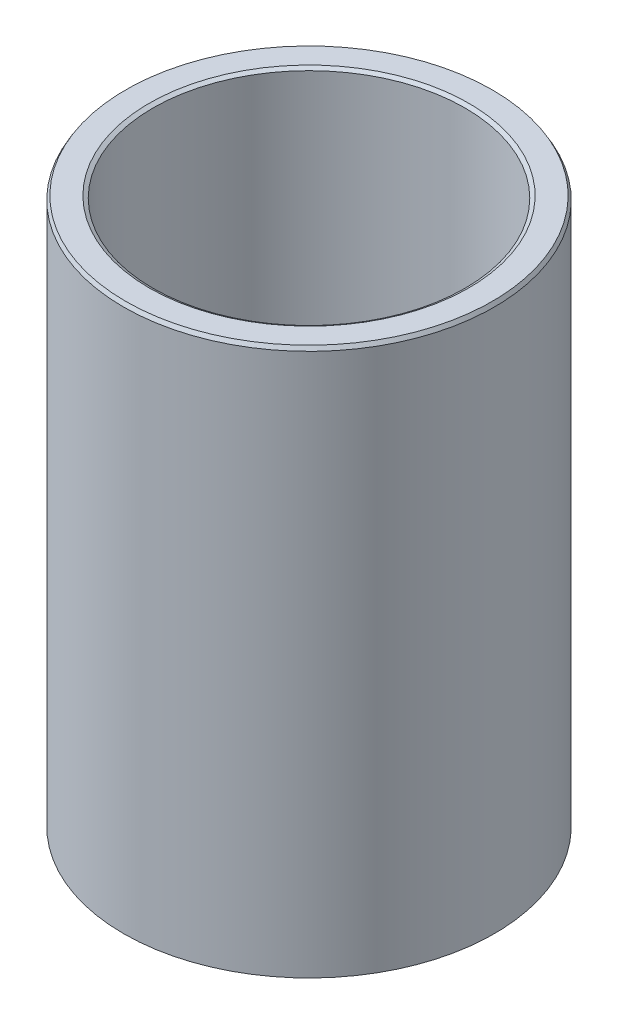
SolidWorks part; units mm, degrees
ref_plane "Front Plane" through (0, 0, 0) normal (0, 0, 1) x (1, 0, 0)
ref_plane "Top Plane" through (0, 0, 0) normal (0, 1, 0) x (1, 0, 0)
ref_plane "Right Plane" through (0, 0, 0) normal (1, 0, 0) x (0, 0, -1)
sketch "Sketch1" plane through (0, 0, 0) normal (0, 1, 0) x (1, 0, 0)
  circle A0 centre (0, 0) radius 37.5
  dimension "SLEEVE_OD" = 75
extrude "Boss-Extrude1" add sketch "Sketch1" along normal blind 110.9538
sketch "Sketch2" plane through (0, 0, 0) normal (0, 1, 0) x (1, 0, 0)
  circle A0 centre (0, 0) radius 31.5702
  dimension "BORE_D" = 63.1403
extrude "Cut-Extrude1" cut sketch "Sketch2" along normal through all
chamfer "Chamfer1" distance 0.7659 angle 30 4 edges at (0, 110.9538, 31.5702) (0, 0, 31.5702) (0, 0, 37.5) (0, 110.9538, 37.5) first distance on face at (0, 110.9538, 31.5702) first distance on face at (0, 0, 31.5702) first distance on face at (0, 110.9538, 37.5)
